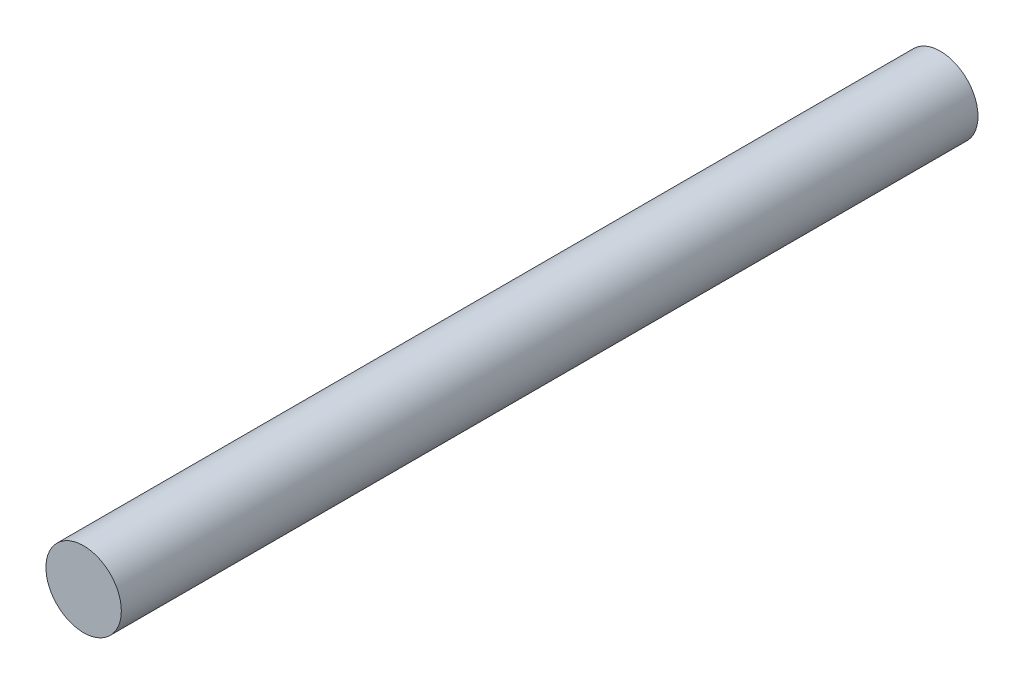
SolidWorks part; units mm, degrees
ref_plane "Płaszczyzna przednia" through (0, 0, 0) normal (0, 0, 1) x (1, 0, 0)
ref_plane "Płaszczyzna górna" through (0, 0, 0) normal (0, 1, 0) x (1, 0, 0)
ref_plane "Płaszczyzna prawa" through (0, 0, 0) normal (1, 0, 0) x (0, 0, -1)
sketch "Szkic1" plane through (0, 0, 0) normal (0, 0, 1) x (1, 0, 0)
  circle A0 centre (0, 0) radius 2.2
  dimension "D1" = 4.4
extrude "Dodanie-wyciągnięcie1" add sketch "Szkic1" along normal blind 50
